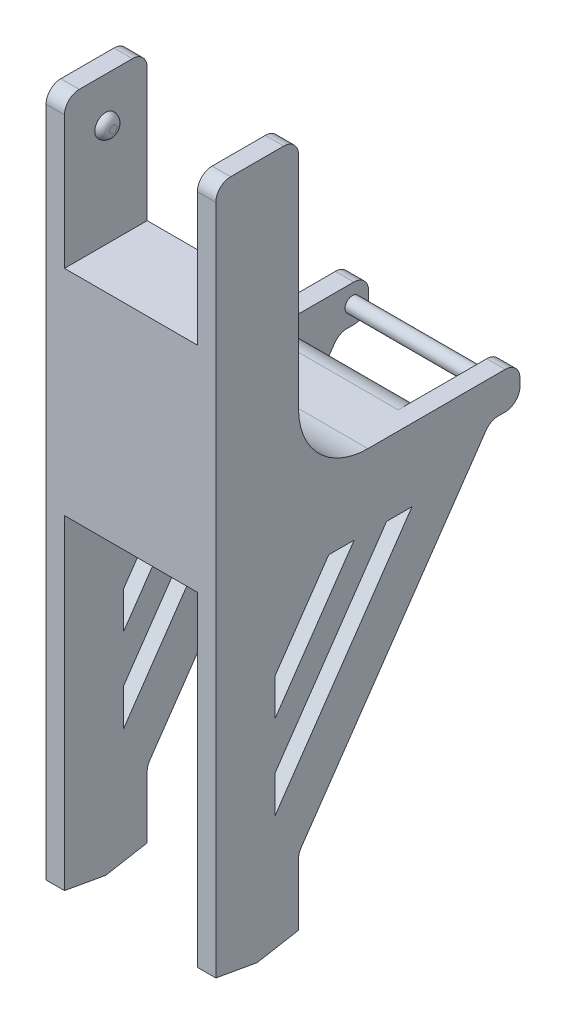
SolidWorks part; units mm, degrees
ref_plane "Front Plane" through (0, 0, 0) normal (0, 0, 1) x (1, 0, 0)
ref_plane "Top Plane" through (0, 0, 0) normal (0, 1, 0) x (1, 0, 0)
ref_plane "Right Plane" through (0, 0, 0) normal (1, 0, 0) x (0, 0, -1)
sketch "Szkic1" plane through (0, 0, 0) normal (1, 0, 0) x (0, 0, -1)
  line L2 (0, 0) -> (-10.3, 0)
  line L5 (-15, 4.7) -> (-15, 20.6)
  line L6 (-15, 20.6) -> (-20.6, 20.6)
  line L7 (-20.6, 20.6) -> (-20.6, -21.4)
  line L8 (0, 0) -> (0, -2.5)
  line L9 (0, -2.5) -> (-2, -2.5)
  line L10 (-2, -2.5) -> (-15, -21.4)
  line L11 (-15, -21.4) -> (-15, -25.9)
  line L13 (-20.6, -25.9) -> (-20.6, -21.4)
  line L20 (-20.6, -25.9) -> (-17.8, -26.4)
  line L21 (-17.8, -26.4) -> (-15, -25.9)
  arc A0 (-15, 4.7) -> (-10.3, 0) centre (-10.3, 4.7) ccw
  point P15 (-10.3, 4.7)
  dimension "D5" = 2.5
  dimension "D7" = 4.7
  dimension "D1" = 42
  dimension "D2" = 20.6
  dimension "D3" = 15.9
  dimension "D4" = 5.6
  dimension "D6" = 2
  dimension "D8" = 18.9
  dimension "D9" = 4.5
  dimension "D10" = 0.5
  dimension "D11" = 4.5
extrude "Dodanie-wyciągnięcie1" add sketch "Szkic1" along normal blind 11.5
ref_plane "Płaszczyzna dolna" through (0, 0, 20.6) normal (0, 0, 1) x (1, 0, 0)
sketch "Szkic2" plane through (0, 0, 20.6) normal (0, 0, 1) x (1, 0, 0)
  line L0 (5.75, 20.6) -> (5.75, -25.9) construction
  line L1 (11.5, 20.6) -> (0, 20.6) construction
  line L4 (10.25, 10.6) -> (1.25, 10.6)
  line L5 (10.25, 10.6) -> (10.25, 20.6)
  line L6 (10.25, 20.6) -> (1.25, 20.6)
  line L7 (1.25, 10.6) -> (1.25, 20.6)
  line L8 (10.25, 10.6) -> (1.25, 20.6) construction
  line L9 (10.25, 20.6) -> (1.25, 10.6) construction
  line L10 (10.25, -3.9) -> (1.25, -3.9)
  line L11 (10.25, -3.9) -> (10.25, -28.2703)
  line L12 (10.25, -28.2703) -> (1.25, -28.2703)
  line L13 (1.25, -3.9) -> (1.25, -28.2703)
  line L14 (10.25, -3.9) -> (1.25, -28.2703) construction
  line L15 (10.25, -28.2703) -> (1.25, -3.9) construction
  point P6 (5.75, 15.6)
  point P11 (5.75, -14.9)
  dimension "D1" = 9
  dimension "D2" = 10
  dimension "D3" = 9
  dimension "D4" = 11
extrude "Wytnij-wyciągnięcie1" cut sketch "Szkic2" against normal through all
ref_plane "Płaszczyzna boczna" through (11.5, 0, 0) normal (1, 0, 0) x (0, 0, -1)
sketch "Szkic3" plane through (11.5, 0, 0) normal (1, 0, 0) x (0, 0, -1)
  line L0 (-16.6, -12.7056) -> (-16.6, -10.1985)
  line L1 (-16.6, -10.1985) -> (-12.9555, -4.9)
  line L2 (-12.9555, -4.9) -> (-11.2311, -4.9)
  line L3 (-11.2311, -4.9) -> (-16.6, -12.7056)
  line L4 (-16.6, -15.8972) -> (-16.6, -18.4043)
  line L5 (-16.6, -18.4043) -> (-7.3113, -4.9)
  line L6 (-7.3113, -4.9) -> (-9.0358, -4.9)
  line L7 (-9.0358, -4.9) -> (-16.6, -15.8972)
  line L8 (-15, -21.4) -> (-2, -2.5) construction
  line L10 (-20.6, 6.325) -> (-20.6, -6.325) construction
  dimension "D1" = 4
  dimension "D2" = 21
extrude "Wytnij-wyciągnięcie2" cut sketch "Szkic3" against normal through all both and the other way through all
ref_plane "Płaszczyzna3" through (0, 0, 0) normal (0, 1, 0) x (1, 0, 0)
sketch "Szkic4" plane through (0, 0, 0) normal (0, 1, 0) x (1, 0, 0)
  line L0 (5.75, -5) -> (5.75, 0) construction
  line L2 (11.5, 0) -> (0, 0) construction
  line L4 (1.25, -5) -> (10.25, -5)
  line L5 (1.25, -5) -> (1.25, 0)
  line L6 (1.25, 0) -> (10.25, 0)
  line L7 (10.25, -5) -> (10.25, 0)
  line L8 (1.25, -5) -> (10.25, 0) construction
  line L9 (1.25, 0) -> (10.25, -5) construction
  point P6 (5.75, -2.5)
  dimension "D1" = 9
  dimension "D2" = 5
extrude "Wytnij-wyciągnięcie3" cut sketch "Szkic4" against normal blind 10
fillet "Zaokrąglenie1" radius 2 2 edges at (5.75, -3.9, 5) (5.75, 0, 5)
fillet "Zaokrąglenie2" radius 1 12 edges at (0.625, 0, 0) (0.625, -2.5, 0) (10.875, -2.5, 0) (10.875, 0, 0) (10.875, 20.6, 20.6) (10.875, 20.6, 15) (0.625, 20.6, 20.6) (0.625, 20.6, 15) (0.625, -2.5, 2) (10.875, -2.5, 2) (0.625, -21.4, 15) (10.875, -21.4, 15)
ref_plane "Płaszczyzna4" through (10.25, 0, 0) normal (-1, 0, 0) x (0, 0, 1)
sketch "Szkic5" plane through (10.25, 0, 0) normal (-1, 0, 0) x (0, 0, 1)
  line L3 (17.8, 20.6) -> (17.8, 10.6) construction
  line L4 (16, 20.6) -> (19.6, 20.6) construction
  line L5 (15, 10.6) -> (20.6, 10.6) construction
  circle A0 centre (17.8, 17.6) radius 0.75
  dimension "D1" = 1.5
  dimension "D2" = 3
extrude "Dodanie-wyciągnięcie2" add sketch "Szkic5" along normal blind 0.5
fillet "Zaokrąglenie3" radius 0.5 1 edges at (9.75, 16.85, 17.8)
ref_plane "Płaszczyzna5" through (5.75, 0, 0) normal (1, 0, 0) x (0, 0, -1)
mirror "Lustro2" about plane through (5.75, 0, 0) normal (1, 0, 0) of bodies 113 115
sketch "Szkic7" plane through (1.25, 0, 0) normal (1, 0, 0) x (0, 0, -1)
  line L0 (0, -1.25) -> (-2.8277, -1.25) construction
  line L1 (0, -1.5) -> (0, -1) construction
  circle A0 centre (-1.1, -1.25) radius 0.5
  dimension "D1" = 1
  dimension "D2" = 1.1
extrude "Dodanie-wyciągnięcie3" add sketch "Szkic7" along normal up to surface (9 mm away) up to face at (10.25, -11.0254, 12.3868)
